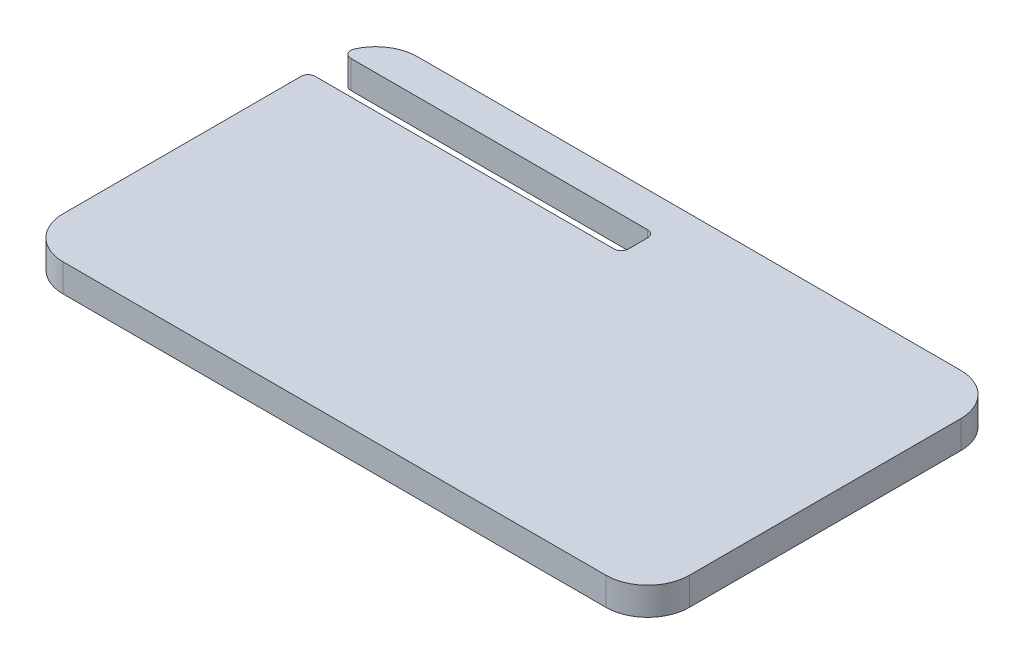
SolidWorks part; units mm, degrees
ref_plane "Alzado" through (0, 0, 0) normal (0, 0, 1) x (1, 0, 0)
ref_plane "Planta" through (0, 0, 0) normal (0, 1, 0) x (1, 0, 0)
ref_plane "Vista lateral" through (0, 0, 0) normal (1, 0, 0) x (0, 0, -1)
sketch "Croquis1" plane through (0, 0, 0) normal (0, 1, 0) x (1, 0, 0)
  line L5 (-22.5, 9.9298) -> (22.5, 9.9298)
  line L6 (-22.5, 9.9298) -> (-22.5, -15.5702)
  line L7 (-22.5, -15.5702) -> (22.5, -15.5702)
  line L8 (22.5, 9.9298) -> (22.5, -15.5702)
  dimension "D1" = 9.9298
  dimension "D2" = 22.5
  dimension "D3" = 25.5
  dimension "D4" = 45
extrude "Saliente-Extruir1" add sketch "Croquis1" along normal blind 2
sketch "Croquis2" plane through (0, 2, 0) normal (0, 1, 0) x (1, 0, 0)
  line L0 (-22.5, 9.9298) -> (-22.5, -15.5702) construction
  line L1 (-22.5, 7.4298) -> (0, 7.4298)
  line L2 (-22.5, 7.4298) -> (-22.5, 5.0298)
  line L3 (-22.5, 5.0298) -> (0, 5.0298)
  line L4 (0, 7.4298) -> (0, 5.0298)
  line L6 (22.5, 9.9298) -> (-22.5, 9.9298) construction
  dimension "D1" = 22.5
  dimension "D2" = 2.5
  dimension "D3" = 2.4
extrude "Cortar-Extruir1" cut sketch "Croquis2" against normal up to surface (2 mm away) up to face at (0, 0, 2.8202)
fillet "Redondeo1" radius 3 4 edges at (-22.5, 1, 15.5702) (-22.5, 1, -9.9298) (22.5, 1, 15.5702) (22.5, 1, -9.9298)
fillet "Redondeo4" radius 0.5 4 edges at (-22.5, 1, -5.0298) (0, 1, -5.0298) (0, 1, -7.4298) (-22.5, 1, -7.4298)
